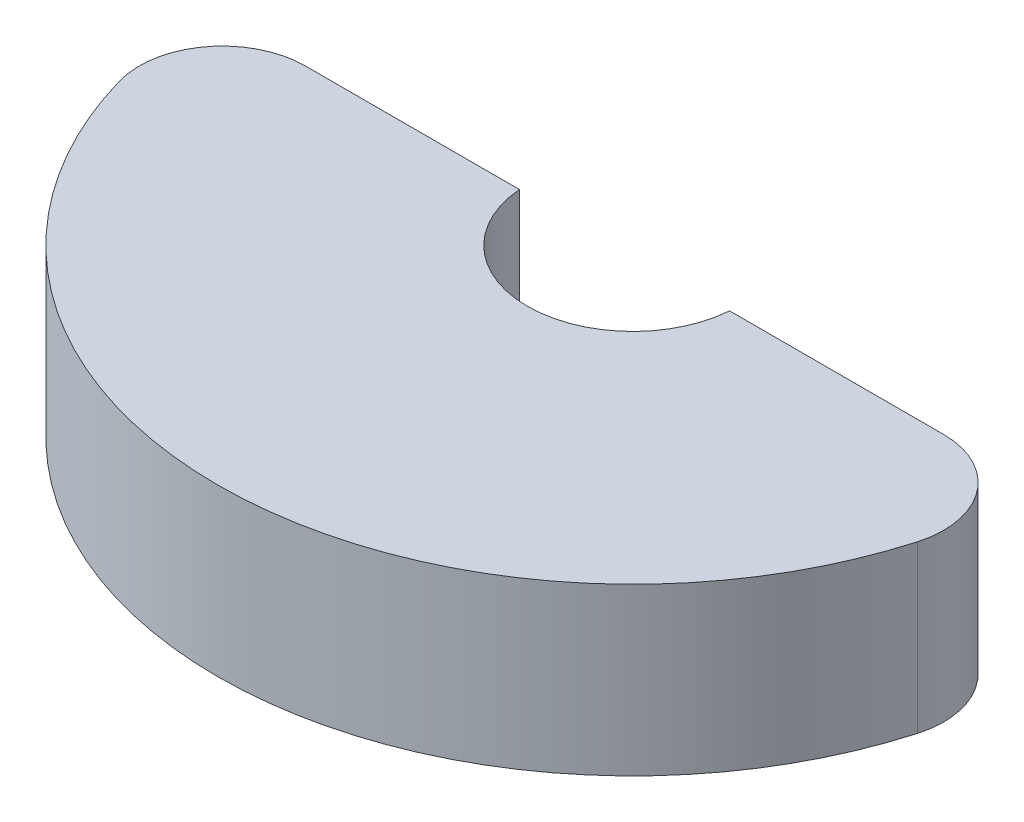
SolidWorks part; units mm, degrees
material "Nylon 101"
ref_plane "Front" through (0, 0, 0) normal (0, 0, 1) x (1, 0, 0)
ref_plane "Top" through (0, 0, 0) normal (0, 1, 0) x (1, 0, 0)
ref_plane "Right" through (0, 0, 0) normal (1, 0, 0) x (0, 0, -1)
sketch "Sketch1" plane through (0, 0, 0) normal (0, 1, 0) x (1, 0, 0)
  line L0 (-25, -50) -> (25, -50) construction
  line L1 (-15, 37.5) -> (15, 37.5) construction
  line L2 (0, -50) -> (0, 50) construction
  line L3 (-25, -50) -> (-25, 50)
  line L4 (25, -50) -> (25, 50)
  line L5 (25, 0) -> (0, 0) construction
  line L6 (25, 17) -> (97.2, 17)
  line L7 (25, 17) -> (25, -17)
  line L8 (25, -17) -> (97.2, -17)
  line L9 (97.2, 17) -> (97.2, -17)
  line L10 (-15, 37.5) -> (-15, -37.5) construction
  line L11 (-15, -37.5) -> (15, -37.5) construction
  line L12 (15, 37.5) -> (15, -37.5) construction
  line L13 (-25, -50.5) -> (25, -50.5)
  line L14 (-25, -49.5) -> (25, -49.5)
  line L15 (-25, 50.5) -> (25, 50.5)
  line L16 (-25, 49.5) -> (25, 49.5)
  circle A0 centre (0, 50) radius 6.35
  circle A1 centre (0, -50) radius 6.35
  arc A2 (-25, -50) -> (25, -50) centre (0, -50) ccw
  arc A3 (25, 50) -> (-25, 50) centre (0, 50) ccw
  circle A6 centre (-15, 37.5) radius 2.5
  circle A7 centre (-15, -37.5) radius 2.5
  circle A8 centre (15, -37.5) radius 2.5
  circle A9 centre (15, 37.5) radius 2.5
  point P8 (0, 0)
  point P24 (0, -37.5)
  dimension "D2" = 12.7
  dimension "D5" = 25
  dimension "D1" = 5
  dimension "D3" = 100
  dimension "D4" = 12.5
  dimension "D6" = 12.5
  dimension "D7" = 34
  dimension "D8" = 72.2
  dimension "D9" = 30
  dimension "D10" = 0.5
  dimension "D11" = 0.5
extrude "Boss-Extrude1" add sketch "Sketch1" along normal blind 10 contours L13 A2 A1 region at (0, 0, 61.3823)
fillet "Fillet1" radius 5 2 edges at (-24.995, 5, 50.5) (24.995, 5, 50.5)
